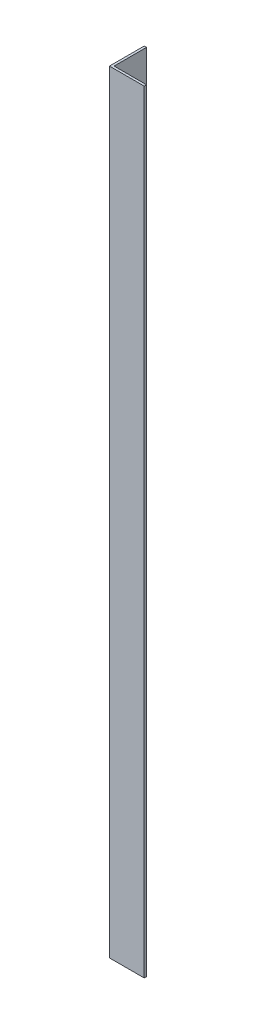
SolidWorks part; units mm, degrees
ref_plane "Спереди" through (0, 0, 0) normal (0, 0, 1) x (1, 0, 0)
ref_plane "Сверху" through (0, 0, 0) normal (0, 1, 0) x (1, 0, 0)
ref_plane "Справа" through (0, 0, 0) normal (1, 0, 0) x (0, 0, -1)
sketch "Эскиз1" plane through (0, 0, 0) normal (0, 1, 0) x (1, 0, 0)
  line L0 (0, 45) -> (0, 0)
  line L1 (0, 0) -> (45, 0)
extrude "Вытянуть-Тонкостенный1" add sketch "Эскиз1" along normal blind 1000 thin thin type one direction reverse wall 3
